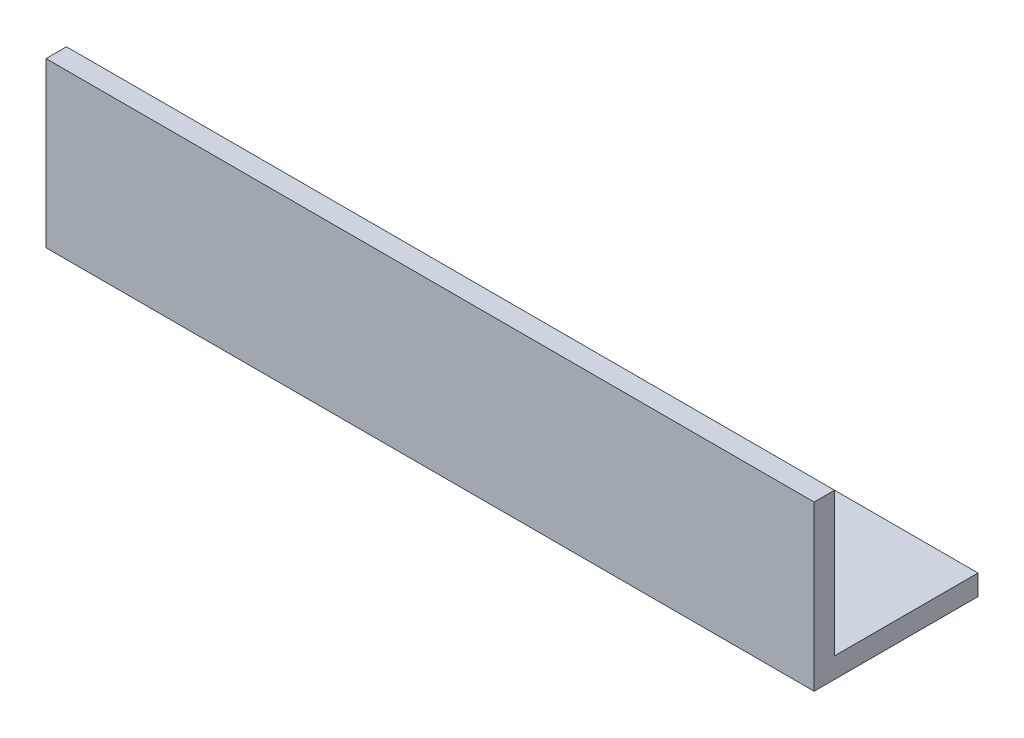
SolidWorks part; units mm, degrees
ref_plane "Спереди" through (0, 0, 0) normal (0, 0, 1) x (1, 0, 0)
ref_plane "Сверху" through (0, 0, 0) normal (0, 1, 0) x (1, 0, 0)
ref_plane "Справа" through (0, 0, 0) normal (1, 0, 0) x (0, 0, -1)
sketch "Эскиз1" plane through (0, 0, 0) normal (1, 0, 0) x (0, 0, -1)
  line L0 (0, 0) -> (0, 32)
  line L1 (0, 0) -> (32, 0)
extrude "Вытянуть-Тонкостенный1" add sketch "Эскиз1" along normal blind 150 thin thin type one direction reverse wall 4
sketch "Эскиз2" plane through (0, 0, 0) normal (0, -1, 0) x (1, 0, 0)
  line L0 (75, -35.2679) -> (75, 2.5217) construction
  circle A0 centre (130, -13) radius 5
  circle A1 centre (100, -13) radius 5
  circle A2 centre (50, -13) radius 5
  circle A3 centre (20, -13) radius 5
  dimension "D1" = 2
extrude "Вырез-Вытянуть1" cut sketch "Эскиз2" against normal through all
